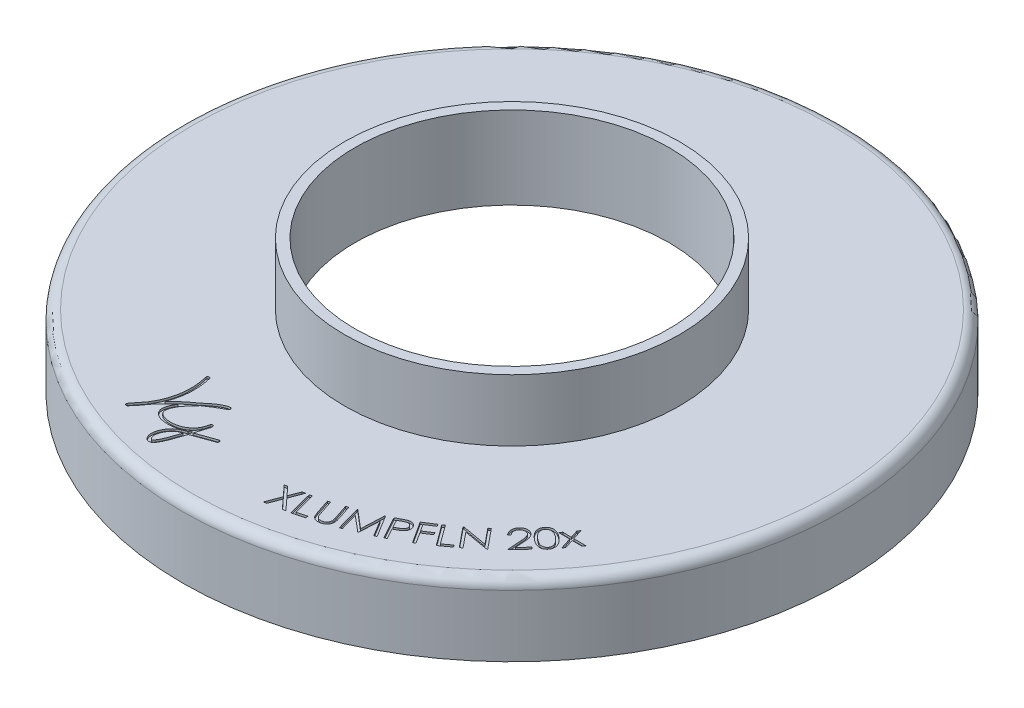
SolidWorks part; units mm, degrees
material "BioMed Black"
ref_plane "Front Plane" through (0, 0, 0) normal (0, 0, 1) x (1, 0, 0)
ref_plane "Top Plane" through (0, 0, 0) normal (0, 1, 0) x (1, 0, 0)
ref_plane "Right Plane" through (0, 0, 0) normal (1, 0, 0) x (0, 0, -1)
sketch "Sketch1" plane through (0, 0, 0) normal (0, 1, 0) x (1, 0, 0)
  circle A0 centre (0, 0) radius 32
  dimension "D1" = 64
extrude "Boss-Extrude1" add sketch "Sketch1" along normal blind 1
sketch "Sketch2" plane through (0, 0, 0) normal (0, -1, 0) x (1, 0, 0)
  circle A0 centre (0, 0) radius 15.25
  dimension "D1" = 30.5
extrude "Cut-Extrude1" cut sketch "Sketch2" against normal through all
sketch "Sketch3" plane through (0, 0, 0) normal (0, -1, 0) x (1, 0, 0)
  circle A0 centre (0, 0) radius 32
  circle A1 centre (0, 0) radius 31.5
  circle A3 centre (0, 0) radius 32 construction
  dimension "D1" = 0.5
extrude "Boss-Extrude2" add sketch "Sketch3" along normal blind 6
sketch "Sketch4" plane through (0, 1, 0) normal (0, 1, 0) x (1, 0, 0)
  circle A0 centre (0, 0) radius 15.25
  circle A1 centre (0, 0) radius 16.25
  circle A2 centre (0, 0) radius 15.25 construction
  point P4 (-15.2226, -0.9137)
  dimension "D1" = 1
extrude "Boss-Extrude3" add sketch "Sketch4" along normal blind 6 and the other way blind 2
fillet "Fillet1" radius 1 1 edges at (0, 1, 32)
sketch "Sketch5" plane through (0, 1, 0) normal (0, 1, 0) x (-1, 0, 0)
  arc A2 (10.5475, 26.744) -> (10.7697, 26.5362) centre (10.6586, 26.6401) cw
  arc A3 (8.8761, 20.4894) -> (9.1721, 20.5598) centre (9.0241, 20.5246) ccw
  arc A4 (10.5343, 26.7277) -> (10.7829, 26.5524) centre (10.6586, 26.6401) cw
  arc A5 (5.3559, 22.193) -> (5.4967, 21.9233) centre (5.4263, 22.0581) ccw
  arc A6 (5.9185, 26.1576) -> (5.8121, 26.4426) centre (5.8653, 26.3001) cw
  arc A7 (4.6798, 24.431) -> (4.9727, 24.3487) centre (4.8263, 24.3898) ccw
  arc A8 (3.2789, 25.2131) -> (3.1764, 25.4995) centre (3.2277, 25.3563) cw
  arc A9 (5.9166, 26.1569) -> (5.8141, 26.4433) centre (5.8653, 26.3001) ccw
  arc A10 (5.4318, 21.9061) -> (5.4208, 22.2101) centre (5.4263, 22.0581) cw
  arc A11 (4.6751, 24.4067) -> (4.9774, 24.3729) centre (4.8263, 24.3898) ccw
  spline S0 degree 2 poles (10.6586, 26.6401) (8.1956, 24.0072) (9.0241, 20.5246) knots 0 0 0 1 1 1 construction
  spline S1 degree 2 poles (10.6586, 26.6401) (8.5937, 23.7116) (5.4263, 22.0581) knots 0 0 0 1 1 1 construction
  spline S2 degree 3 poles (5.4263, 22.0581) (6.3799, 22.0926) (10.2082, 25.6921) (6.3521, 26.4783) (5.0792, 25.3888) (4.852, 24.5685) (4.8316, 24.4373) (4.8263, 24.3898) knots 0 0 0 0 0.530866 0.72538 0.957095 0.984557 1 1 1 1 construction
  spline S3 degree 3 poles (5.8653, 26.3001) (6.5714, 26.5635) (7.2534, 27.8751) (6.3675, 28.9607) (5.8422, 28.0063) (4.8263, 24.3898) knots 0 0 0 0 0.452994 0.552994 1 1 1 1 construction
  spline S4 degree 1 poles (3.2277, 25.3563) (5.8653, 26.3001) knots 0 0 1 1 construction
  spline S11 degree 2 poles (10.5475, 26.744) (8.0312, 24.0514) (8.8761, 20.4894) knots 0 0 0 1 1 1
  spline S13 degree 2 poles (10.7697, 26.5362) (8.3599, 23.963) (9.1721, 20.5598) knots 0 0 0 1 1 1
  spline S15 degree 2 poles (10.5343, 26.7277) (8.4907, 23.8292) (5.3559, 22.193) knots 0 0 0 1 1 1
  spline S17 degree 2 poles (10.7829, 26.5524) (8.6968, 23.594) (5.4967, 21.9233) knots 0 0 0 1 1 1
  spline S19 degree 3 poles (5.9185, 26.1576) (6.3717, 26.3267) (6.8984, 26.9544) (7.1709, 27.8934) (7.0135, 28.4415) (6.7357, 28.709) (6.3154, 28.761) (6.0293, 28.3908) (5.7014, 27.6737) (5.4175, 26.8922) (5.1383, 26.0114) (4.8892, 25.1689) (4.7472, 24.6708) (4.6798, 24.431) knots 0 0 0 0 0.25 0.375 0.5 0.5625 0.625 0.75 0.8125 0.875 0.9375 0.96875 1 1 1 1
  spline S21 degree 3 poles (5.8121, 26.4426) (5.9954, 26.511) (6.3045, 26.7422) (6.6925, 27.3191) (6.8485, 27.9236) (6.7424, 28.2885) (6.5593, 28.429) (6.5334, 28.4322) (6.4149, 28.369) (6.2188, 28.0773) (5.985, 27.5615) (5.7062, 26.7964) (5.4293, 25.9226) (5.1814, 25.0843) (5.0399, 24.5877) (4.9727, 24.3487) knots 0 0 0 0 0.125 0.25 0.375 0.5 0.5625 0.625 0.6875 0.75 0.8125 0.875 0.9375 0.96875 1 1 1 1
  spline S23 degree 1 poles (3.2789, 25.2131) (5.9166, 26.1569) knots 0 0 1 1
  spline S25 degree 1 poles (3.1764, 25.4995) (5.8141, 26.4433) knots 0 0 1 1
  spline S27 degree 3 poles (5.4318, 21.9061) (5.5912, 21.9119) (5.8735, 22.0048) (6.5962, 22.4138) (7.5826, 23.2586) (8.5251, 24.4716) (8.7986, 25.4706) (8.3112, 26.0811) (7.5144, 26.3909) (5.7553, 26.3608) (4.7664, 25.2231) (4.6751, 24.4067) knots 0 0 0 0 0.0625 0.125 0.25 0.375 0.5 0.5625 0.625 0.75 1 1 1 1
  spline S29 degree 3 poles (5.4208, 22.2101) (5.4718, 22.212) (5.559, 22.2284) (5.833, 22.3277) (6.2411, 22.5633) (6.79, 22.9827) (7.5131, 23.6633) (8.2711, 24.6485) (8.4385, 25.4407) (8.147, 25.8028) (7.478, 26.0869) (5.8933, 26.0473) (5.0564, 25.0785) (4.9774, 24.3729) knots 0 0 0 0 0.03125 0.0625 0.125 0.1875 0.25 0.375 0.5 0.5625 0.625 0.75 1 1 1 1
extrude "Tag" cut sketch "Sketch5" against normal blind 0.2 contours S19 A7 S21 A6 | S27 A11 S29 A10 | S25 A9 S23 A8 | S15 A5 S17 A4 | S11 A3 S13 A2
sketch "Sketch6" plane through (0, 1, 0) normal (0, 1, 0) x (1, 0, 0)
  arc A0 (-0.5755, -28.5534) -> (25.7476, -12.3567) centre (0, 0) ccw construction
  text T1 "XLUMPFLN 20x" font "Century Gothic" height 2.5
extrude "Compatibility text" cut sketch "Sketch6" against normal blind 0.2
